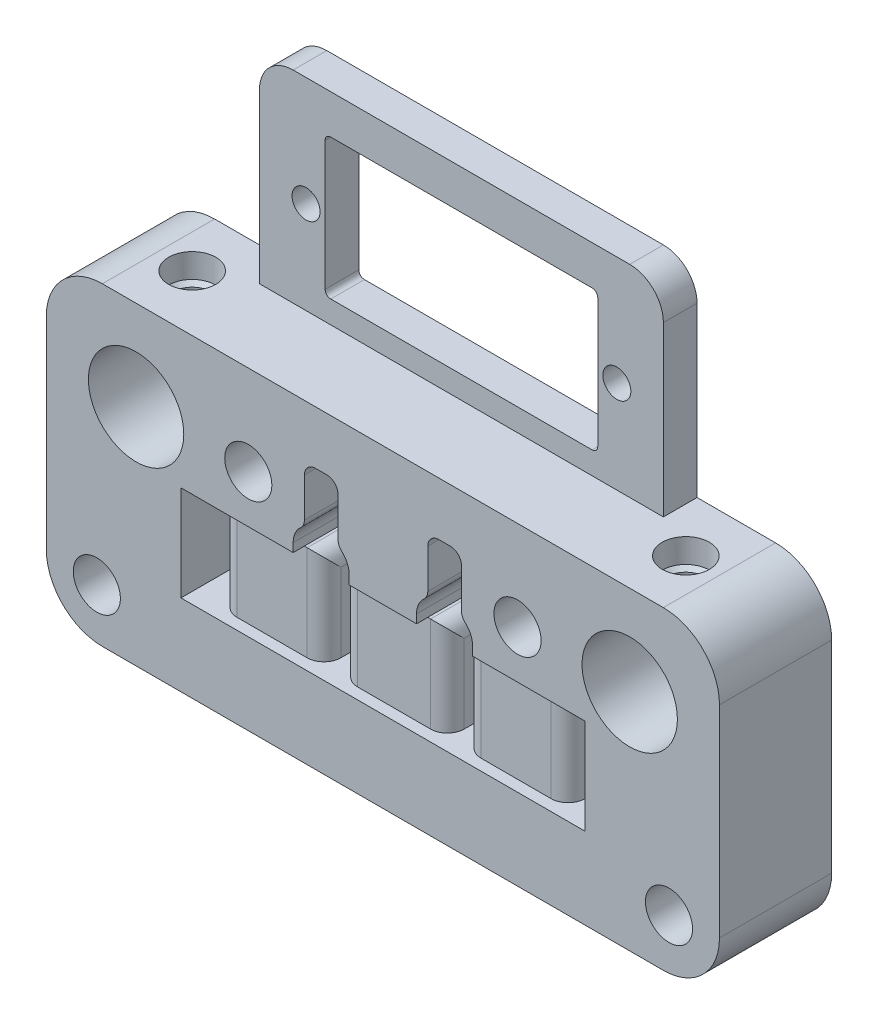
SolidWorks part; units mm, degrees
ref_plane "Front Plane" through (0, 0, 0) normal (0, 0, 1) x (1, 0, 0)
ref_plane "Top Plane" through (0, 0, 0) normal (0, 1, 0) x (1, 0, 0)
ref_plane "Right Plane" through (0, 0, 0) normal (1, 0, 0) x (0, 0, -1)
sketch "Sketch1" plane through (0, 0, 0) normal (0, 0, 1) x (1, 0, 0)
  line L0 (-30, 14) -> (30, -14) construction
  line L1 (-30, 14) -> (30, 14)
  line L2 (-30, 14) -> (-30, -14)
  line L3 (-30, -14) -> (30, -14)
  line L4 (30, 14) -> (30, -14)
  line L5 (0, 0) -> (0, 36.8289) construction
  circle A0 centre (-22, 6) radius 4.25
  circle A1 centre (22, 6) radius 4.25
  point P4 (0, 0)
  point P12 (26.25, 6)
  dimension "D3" = 8.5
  dimension "D1" = 60
  dimension "D2" = 28
  dimension "D4" = 44
  dimension "D5" = 8
  dimension "D6" = 8
  dimension "D7" = 3.75
extrude "Boss-Extrude1" add sketch "Sketch1" along normal mid plane 10
sketch "Sketch2" plane through (0, 0, -5) normal (0, 0, -1) x (-1, 0, 0)
  line L0 (8, -6.75) -> (-8, 4.25) construction
  line L1 (8, -6.75) -> (3, -6.75)
  line L2 (8, -6.75) -> (8, 4.25)
  line L3 (8, 4.25) -> (7, 4.25)
  line L4 (-8, -6.75) -> (-8, 4.25)
  line L5 (0, -1.25) -> (0, -22.2532) construction
  line L6 (-3, 4.25) -> (-3, -6.75)
  line L7 (30, -14) -> (-30, -14) construction
  line L8 (3, 4.25) -> (3, -6.75)
  line L9 (-3, 4.25) -> (-4, 4.25)
  line L10 (-3, -6.75) -> (-8, -6.75)
  line L11 (-7, 4.25) -> (-7, 9.25)
  line L12 (-7, 9.25) -> (-4, 9.25)
  line L13 (-4, 9.25) -> (-4, 4.25)
  line L14 (4, 4.25) -> (4, 9.25)
  line L15 (4, 9.25) -> (7, 9.25)
  line L16 (7, 9.25) -> (7, 4.25)
  line L17 (-7, 4.25) -> (-8, 4.25)
  line L18 (4, 4.25) -> (3, 4.25)
  line L19 (-3, 4.25) -> (-8, -6.75) construction
  line L20 (8, 4.25) -> (3, -6.75) construction
  line L21 (5.5, -1.25) -> (5.5, 15.8712) construction
  line L22 (-5.5, -1.25) -> (-5.5, 16.3359) construction
  dimension "D1" = 11
  dimension "D2" = 16
  dimension "D3" = 7.25
  dimension "D4" = 6
  dimension "D5" = 3
  dimension "D6" = 5
extrude "Cut-Extrude1" cut sketch "Sketch2" against normal through all
sketch "Sketch3" plane through (0, 14, 0) normal (0, 1, 0) x (1, 0, 0)
  line L0 (0, 0) -> (0, 24.2319) construction
  circle A0 centre (-22, 0) radius 1.75
  circle A1 centre (22, 0) radius 1.75
  dimension "D1" = 3.5
  dimension "D2" = 44
extrude "Cut-Extrude2" cut sketch "Sketch3" against normal up to next
fillet "Fillet1" radius 5 4 edges at (30, 14, 0) (30, -14, 0) (-30, -14, 0) (-30, 14, 0)
fillet "Fillet2" radius 2 4 edges at (-8, 4.25, 0) (3, 4.25, 0) (-3, 4.25, 0) (8, 4.25, 0)
sketch "Sketch4" plane through (0, 0, -5) normal (0, 0, -1) x (-1, 0, 0)
  line L0 (-25, 14) -> (25, 14) construction
  line L1 (-18, 14) -> (18, 14)
  line L2 (-18, 14) -> (-18, 29)
  line L3 (-15, 32) -> (15, 32)
  line L4 (18, 14) -> (18, 29)
  line L5 (0, 0) -> (0, 55.0176) construction
  line L6 (-12.15, 28.5) -> (12.15, 16) construction
  line L7 (-11.65, 28.5) -> (11.65, 28.5)
  line L8 (-12.15, 28) -> (-12.15, 16.5)
  line L9 (-11.65, 16) -> (11.65, 16)
  line L10 (12.15, 28) -> (12.15, 16.5)
  line L11 (0, 22.25) -> (13.85, 22.25) construction
  circle A0 centre (-13.85, 22.25) radius 1.25
  circle A1 centre (13.85, 22.25) radius 1.25
  arc A2 (18, 29) -> (15, 32) centre (15, 29) ccw
  arc A3 (-18, 29) -> (-15, 32) centre (-15, 29) cw
  arc A4 (11.65, 28.5) -> (12.15, 28) centre (11.65, 28) cw
  arc A5 (11.65, 16) -> (12.15, 16.5) centre (11.65, 16.5) ccw
  arc A6 (-12.15, 16.5) -> (-11.65, 16) centre (-11.65, 16.5) ccw
  arc A7 (-11.65, 28.5) -> (-12.15, 28) centre (-11.65, 28) ccw
  point P20 (18, 32)
  point P25 (12.15, 28.5)
  dimension "D5" = 27.7
  dimension "D7" = 2.5
  dimension "D8" = 3
  dimension "D9" = 0.5
  dimension "D1" = 36
  dimension "D2" = 18
  dimension "D3" = 24.3
  dimension "D4" = 12.5
  dimension "D6" = 2
extrude "Boss-Extrude2" add sketch "Sketch4" against normal blind 3
sketch "Sketch5" plane through (0, 0, 5) normal (0, 0, 1) x (1, 0, 0)
  line L1 (-10, 1.75) -> (-6.25, 1.75)
  line L2 (-10, 1.75) -> (-10, -6.75)
  line L3 (-10, -6.75) -> (-6.25, -6.75)
  line L4 (-6.25, 1.75) -> (-6.25, -6.75)
  line L5 (-3, -6.75) -> (-8, -6.75) construction
  line L6 (0, 0) -> (0, -11.1348) construction
  line L7 (-4.75, 1.75) -> (4.75, 1.75)
  line L8 (-4.75, 1.75) -> (-4.75, -6.75)
  line L9 (-4.75, -6.75) -> (4.75, -6.75)
  line L14 (4.75, 1.75) -> (4.75, -6.75)
  line L15 (6.25, 1.75) -> (10, 1.75)
  line L16 (6.25, 1.75) -> (6.25, -6.75)
  line L17 (6.25, -6.75) -> (10, -6.75)
  line L18 (10, 1.75) -> (10, -6.75)
  line L19 (-6.25, 1.75) -> (-4.75, -6.75) construction
  line L20 (4.75, 1.75) -> (6.25, -6.75) construction
  line L21 (8, -6.75) -> (3, -6.75) construction
  point P4 (-5.5, -2.0454)
  point P9 (-5.5, -2.5)
  point P11 (5.5, -2.5)
  point P12 (0, 0)
  point P14 (0, 0)
  dimension "D1" = 1.5
  dimension "D2" = 9.5
  dimension "D3" = 5.5
  dimension "D4" = 8.5
  dimension "D5" = 5.5
  dimension "D6" = 11
extrude "Boss-Extrude4" add sketch "Sketch5" against normal up to surface (10 mm away) up to face at (-5.5, 2.3505, -5)
sketch "Sketch6" plane through (0, 0, 5) normal (0, 0, 1) x (1, 0, 0)
  line L0 (4.75, 1.75) -> (3, 1.75) construction
  line L1 (-18, 1.75) -> (18, 1.75)
  line L2 (-18, 1.75) -> (-18, -6.75)
  line L3 (-18, -6.75) -> (18, -6.75)
  line L4 (18, 1.75) -> (18, -6.75)
  line L7 (0, 0) -> (0, 25.4037) construction
  dimension "D1" = 8.5
  dimension "D2" = 36
extrude "Cut-Extrude3" cut sketch "Sketch6" against normal blind 1
sketch "Sketch7" plane through (0, 0, 5) normal (0, 0, 1) x (1, 0, 0)
  line L0 (0, 0) -> (0, -21.3369) construction
  line L1 (25, 14) -> (-25, 14) construction
  line L2 (-25, -14) -> (25, -14) construction
  line L4 (30, -9) -> (30, 9) construction
  line L5 (-18, -2.5) -> (18, -2.5) construction
  line L6 (-18, 1.75) -> (-18, -6.75) construction
  line L7 (18, -6.75) -> (18, 1.75) construction
  circle A1 centre (25.5, -9.5) radius 1.75
  circle A2 centre (-25.5, -9.5) radius 1.75
  circle A3 centre (-12, 6) radius 1.75
  circle A4 centre (12, 6) radius 1.75
  dimension "D1" = 4.5
  dimension "D4" = 8
  dimension "D2" = 3.5
  dimension "D3" = 24
  dimension "D5" = 4.5
extrude "Cut-Extrude4" cut sketch "Sketch7" against normal through all
sketch "Sketch8" plane through (0, 0, 5) normal (0, 0, -1) x (-1, 0, 0)
  circle A0 centre (-12, 6) radius 2.1
  circle A1 centre (-25.5, -9.5) radius 2.1
  circle A2 centre (25.5, -9.5) radius 2.1
  circle A3 centre (12, 6) radius 2.1
  dimension "D1" = 4.2
extrude "Cut-Extrude5" cut sketch "Sketch8" along normal blind 4
sketch "Sketch9" plane through (0, 14, 0) normal (0, -1, 0) x (1, 0, 0)
  circle A0 centre (-22, 0) radius 2.1
  circle A1 centre (22, 0) radius 2.1
  dimension "D1" = 4.2
extrude "Cut-Extrude6" cut sketch "Sketch9" along normal blind 2
chamfer "Chamfer1" distance 0.5 angle 45 6 edges at (-27.25, -9.5, 1) (23.75, -9.5, 1) (-22, 12, -1.75) (22, 12, -1.75) (-13.75, 6, 1) (10.25, 6, 1)
sketch "Sketch10" plane through (0, 0, 4) normal (0, 0, 1) x (1, 0, 0)
  line L0 (18, -6.75) -> (-18, -6.75) construction
  line L1 (-18, 1.75) -> (-15.5, 1.75)
  line L2 (-18, 1.75) -> (-18, -6.75)
  line L3 (-18, -6.75) -> (-15.5, -6.75)
  line L4 (-15.5, 1.75) -> (-15.5, -6.75)
  line L6 (18, 1.75) -> (15.5, 1.75)
  line L7 (18, 1.75) -> (18, -6.75)
  line L8 (18, -6.75) -> (15.5, -6.75)
  line L9 (15.5, 1.75) -> (15.5, -6.75)
  dimension "D1" = 2.5
extrude "Cut-Extrude7" cut sketch "Sketch10" against normal up to next
fillet "Fillet3" radius 1.5 10 edges at (6.25, 1.75, -0.5) (4.75, -2.5, 4) (6.25, -2.5, 4) (-4.75, 1.75, -0.5) (-4.75, -2.5, 4) (-6.25, 1.75, -0.5) (-6.25, -2.5, 4) (15.5, -2.5, 4) (-15.5, -2.5, 4) (4.75, 1.75, -0.5)
fillet "Fillet4" radius 1 8 edges at (4, 9.25, 0) (7, 9.25, 0) (-4, 9.25, 0) (-7, 9.25, 0) (7, 4.25, 0) (4, 4.25, 0) (-4, 4.25, 0) (-7, 4.25, 0)
